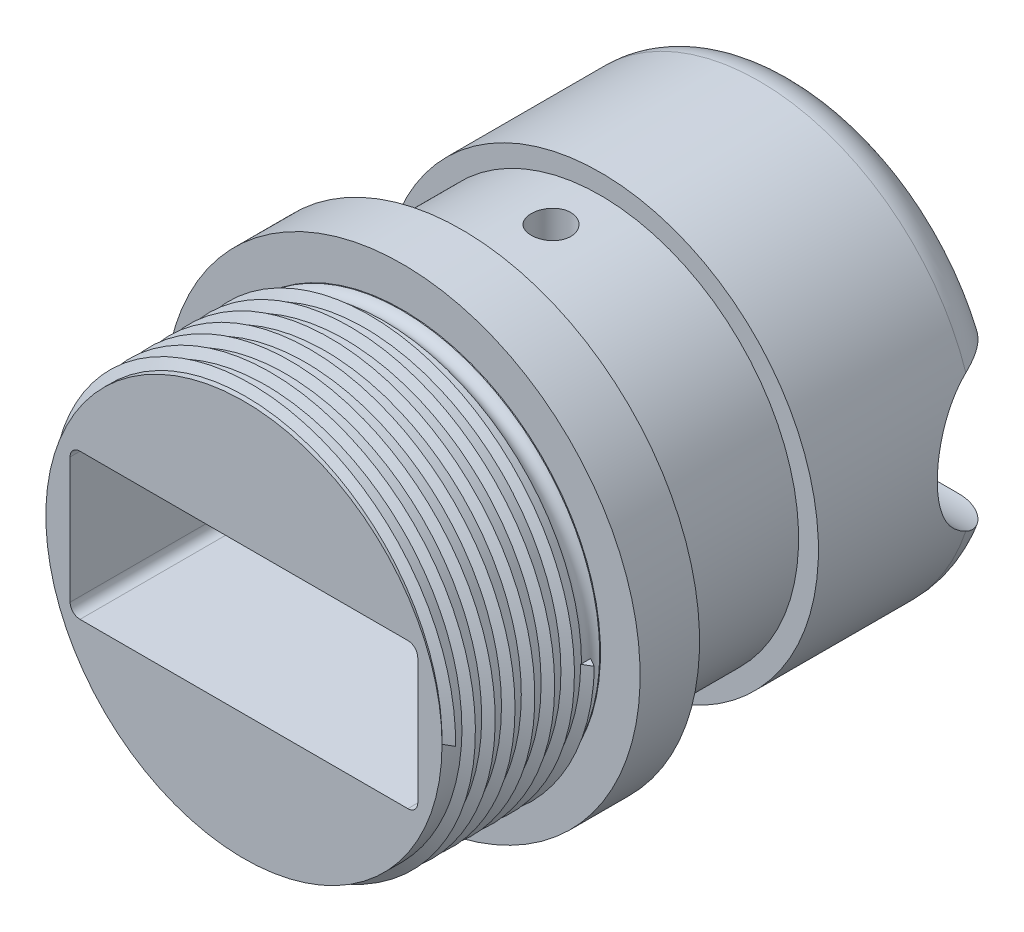
SolidWorks part; units mm, degrees
ref_plane "前视基准面" through (0, 0, 0) normal (0, 0, 1) x (1, 0, 0)
ref_plane "上视基准面" through (0, 0, 0) normal (0, 1, 0) x (1, 0, 0)
ref_plane "右视基准面" through (0, 0, 0) normal (1, 0, 0) x (0, 0, -1)
sketch "草图2" plane through (0, 0, 0) normal (0, 1, 0) x (1, 0, 0)
  line L0 (0, 26.9047) -> (0, -24.3553) construction
  line L1 (0, 20) -> (11, 20)
  line L2 (11, 20) -> (11, 10)
  line L3 (11, 10) -> (10, 10)
  line L4 (10, 10) -> (10, 3)
  line L5 (10, 3) -> (12, 3)
  line L6 (12, 3) -> (12, 0)
  line L7 (12, 0) -> (10, 0)
  line L8 (10, 0) -> (10, -8)
  line L9 (10, -8) -> (0, -8)
  line L10 (0, -8) -> (0, 20)
  dimension "D1" = 10
  dimension "D2" = 2
  dimension "D3" = 11
  dimension "D4" = 1
  dimension "D5" = 7
  dimension "D6" = 3
  dimension "D7" = 10
  dimension "D8" = 8
revolve "旋转1" add sketch "草图2" angle 360 about L0
fillet "圆角1" radius 2 1 edges at (-11, 0, -20)
ref_plane "基准面1" through (3, 0, 0) normal (1, 0, 0) x (0, 0, -1)
sketch "草图6" plane through (3, 0, 0) normal (1, 0, 0) x (0, 0, -1)
  line L0 (20, -9) -> (20, 9) construction
  circle A0 centre (20, 0) radius 4
extrude "切除-拉伸2" cut sketch "草图6" along normal blind 8 and the other way blind 1.5
mirror "镜向1" about plane through (0, 0, 0) normal (1, 0, 0) of "切除-拉伸2"
sketch "草图7" plane through (0, 0, 0) normal (1, 0, 0) x (0, 0, -1)
  line L0 (18, 1.8177) -> (18, -1.6373) construction
  line L1 (18.6831, 1.8177) -> (18.6831, -1.6373)
  line L2 (17.3169, 1.8177) -> (17.3169, -1.6373)
  line L3 (20, -4) -> (20, 4) construction
  arc A0 (18.6831, 1.8177) -> (17.3169, 1.8177) centre (18, 1.8177) ccw
  arc A1 (17.3169, -1.6373) -> (18.6831, -1.6373) centre (18, -1.6373) ccw
  point P2 (18, 0.0902)
  dimension "D1" = 2
extrude "切除-拉伸3" cut sketch "草图7" against normal blind 8 and the other way blind 8
sketch "草图11" plane through (0, 0, 0) normal (1, 0, 0) x (0, 0, -1)
  line L3 (0, 12.1) -> (0, -12.1) construction
  circle A0 centre (-0.5, 10.2) radius 0.5
  dimension "D1" = 10.2
  dimension "D2" = 1
sketch "草图12" plane through (0, 0, 0) normal (1, 0, 0) x (0, 0, -1)
  line L0 (-8.2247, 0) -> (7.843, 0) construction
revolve "切除-旋转1" cut sketch "草图11" angle 360 about L0
sketch "草图13" plane through (0, 0, 8) normal (0, 0, 1) x (1, 0, 0)
  line L0 (0, -13.2) -> (0, 13.2) construction
  line L1 (8.775, -3.675) -> (-8.775, -3.675)
  line L2 (8.775, -3.675) -> (8.775, 3.675)
  line L3 (8.775, 3.675) -> (-8.775, 3.675)
  line L4 (-8.775, -3.675) -> (-8.775, 3.675)
  line L5 (13.2, 0) -> (-13.2, 0) construction
  dimension "D1" = 17.55
  dimension "D2" = 7.35
  dimension "D3" = 8.775
  dimension "D4" = 3.675
extrude "切除-拉伸4" cut sketch "草图13" against normal blind 18
fillet "圆角2" radius 0.5 4 edges at (8.775, -3.675, -1) (8.775, 3.675, -1) (-8.775, 3.675, -1) (-8.775, -3.675, -1)
ref_plane "基准面5" through (0, 10, 0) normal (0, 1, 0) x (1, 0, 0)
sketch "草图15" plane through (0, 10, 0) normal (0, 1, 0) x (1, 0, 0)
  line L0 (8.9137, 10) -> (-10.7147, 10) construction
  line L1 (-11, 10) -> (11, 10) construction
  line L6 (0, -8.2247) -> (0, 7.843) construction
  line L7 (0, 6.293) -> (0, 12.928) construction
  circle A0 centre (0, 7.5) radius 1
  dimension "D1" = 2.5
extrude "切除-拉伸5" cut sketch "草图15" against normal blind 4.5
sketch "草图16" plane through (0, 5.5, 0) normal (0, 1, 0) x (1, 0, 0)
  circle A0 centre (0, 7.5) radius 0.5
extrude "切除-拉伸6" cut sketch "草图16" against normal blind 6
mirror "镜向3" about plane through (0, 0, 0) normal (0, 1, 0) of "切除-拉伸6", "切除-拉伸5"
sketch "草图22" plane through (0, 0, 8) normal (0, 0, 1) x (1, 0, 0)
  circle A0 centre (0, 0) radius 10
curve "螺旋线/涡状线1" pitch 1 height 7 radius 10 left hand yes centre (0, 0, 8) axis (0, 0, -1) start towards (1, 0, 0)
ref_plane "基准面9" through (10, 0, 8) normal (0, 0.9999, -0.0159) x (1, 0, 0)
sketch "草图34" plane through (0, 0, 0) normal (0, 1, 0) x (1, 0, 0)
  line L0 (10, -8) -> (10, -7.5)
  line L1 (10, -8) -> (10, -0.9583) construction
  line L2 (10, -7.5) -> (10.433, -7.75)
  line L3 (10.433, -7.75) -> (10, -8)
  dimension "D1" = 0.5
  dimension "D2" = 60
  dimension "D3" = 60
sweep "扫描1" add profiles "草图34" path "螺旋线/涡状线1"
